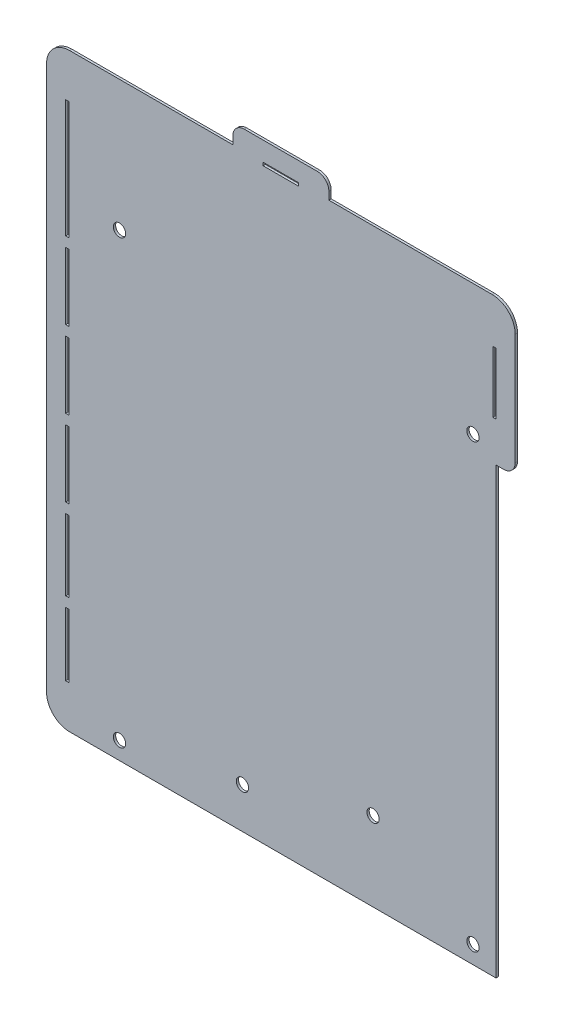
SolidWorks part; units mm, degrees
material "Plain Carbon Steel"
ref_plane "Front Plane" through (0, 0, 0) normal (0, 0, 1) x (1, 0, 0)
ref_plane "Top Plane" through (0, 0, 0) normal (0, 1, 0) x (1, 0, 0)
ref_plane "Right Plane" through (0, 0, 0) normal (1, 0, 0) x (0, 0, -1)
sketch "Model" plane through (0, 0, 0) normal (0, 0, 1) x (1, 0, 0)
  line L0 (104.1673, 32.1811) -> (4.1672, 32.1811)
  line L1 (104.1673, 155.1806) -> (104.1673, 32.1811)
  line L2 (4.1672, 155.1806) -> (104.1673, 155.1806)
  line L3 (4.1672, 32.1811) -> (4.1672, 155.1806)
  line L4 (44.9158, 146.4259) -> (47.4224, 146.4259)
  line L5 (47.4224, 146.4259) -> (47.4224, 148.9326)
  line L6 (47.4224, 148.9326) -> (44.9158, 148.9326)
  line L7 (44.9158, 148.9326) -> (44.9158, 146.4259)
  line L8 (77.4127, 147.4278) -> (79.9193, 147.4278)
  line L9 (79.9193, 147.4278) -> (79.9193, 149.9344)
  line L10 (79.9193, 149.9344) -> (77.4127, 149.9344)
  line L11 (77.4127, 149.9344) -> (77.4127, 147.4278)
  line L12 (6.3266, 141.9721) -> (8.3592, 141.9721)
  line L13 (8.3592, 141.9721) -> (8.3592, 144.0047)
  line L14 (8.3592, 144.0047) -> (6.3266, 144.0047)
  line L15 (6.3266, 144.0047) -> (6.3266, 141.9721)
  line L16 (6.3266, 121.6529) -> (8.3592, 121.6529)
  line L17 (8.3592, 121.6529) -> (8.3592, 123.6855)
  line L18 (8.3592, 123.6855) -> (6.3266, 123.6855)
  line L19 (6.3266, 123.6855) -> (6.3266, 121.6529)
  line L20 (6.3266, 101.3324) -> (8.3592, 101.3324)
  line L21 (8.3592, 101.3324) -> (8.3592, 103.365)
  line L22 (8.3592, 103.365) -> (6.3266, 103.365)
  line L23 (6.3266, 103.365) -> (6.3266, 101.3324)
  line L24 (6.3266, 81.0118) -> (8.3592, 81.0118)
  line L25 (8.3592, 81.0118) -> (8.3592, 83.0444)
  line L26 (8.3592, 83.0444) -> (6.3266, 83.0444)
  line L27 (6.3266, 83.0444) -> (6.3266, 81.0118)
  line L28 (6.3266, 60.6927) -> (8.3592, 60.6927)
  line L29 (8.3592, 60.6927) -> (8.3592, 62.7253)
  line L30 (8.3592, 62.7253) -> (6.3266, 62.7253)
  line L31 (6.3266, 62.7253) -> (6.3266, 60.6927)
  line L32 (85.9221, 148.4144) -> (87.9547, 148.4144)
  line L33 (87.9547, 148.4144) -> (87.9547, 150.447)
  line L34 (87.9547, 150.447) -> (85.9221, 150.447)
  line L35 (85.9221, 150.447) -> (85.9221, 148.4144)
  line L36 (6.3266, 50.5324) -> (8.3592, 50.5324)
  line L37 (8.3592, 50.5324) -> (8.3592, 52.565)
  line L38 (8.3592, 52.565) -> (6.3266, 52.565)
  line L39 (6.3266, 52.565) -> (6.3266, 50.5324)
  line L40 (6.3266, 42.9118) -> (8.3592, 42.9118)
  line L41 (8.3592, 42.9118) -> (8.3592, 44.9444)
  line L42 (8.3592, 44.9444) -> (6.3266, 44.9444)
  line L43 (6.3266, 44.9444) -> (6.3266, 42.9118)
  line L44 (52.8726, 50.0418) -> (54.3815, 50.0418)
  line L45 (54.3815, 50.0418) -> (54.3815, 51.5508)
  line L46 (54.3815, 51.5508) -> (52.8726, 51.5508)
  line L47 (52.8726, 51.5508) -> (52.8726, 50.0418)
  line L48 (58.4219, 130.1637) -> (60.4545, 130.1637)
  line L49 (60.4545, 130.1637) -> (60.4545, 132.1963)
  line L50 (60.4545, 132.1963) -> (58.4219, 132.1963)
  line L51 (58.4219, 132.1963) -> (58.4219, 130.1637)
  line L52 (97.8807, 141.1439) -> (99.9133, 141.1439)
  line L53 (99.9133, 141.1439) -> (99.9133, 143.1765)
  line L54 (99.9133, 143.1765) -> (97.8807, 143.1765)
  line L55 (97.8807, 143.1765) -> (97.8807, 141.1439)
  line L56 (48.438, 37.3046) -> (48.438, 37.0552)
  line L57 (49.9456, 37.0552) -> (49.9456, 37.3046)
  line L58 (52.8877, 37.3046) -> (52.8877, 37.0552)
  line L59 (54.3967, 37.0552) -> (54.3967, 37.3046)
  line L60 (54.3126, 34.0993) -> (54.3126, 33.8995)
  line L61 (56.7201, 33.8995) -> (56.7201, 34.0993)
  line L62 (46.1133, 34.0993) -> (46.1133, 33.8995)
  line L63 (48.5207, 33.8995) -> (48.5207, 34.0993)
  line L64 (82.9607, 49.0165) -> (84.9933, 49.0165)
  line L65 (84.9933, 49.0165) -> (84.9933, 51.0492)
  line L66 (84.9933, 51.0492) -> (82.9607, 51.0492)
  line L67 (82.9607, 51.0492) -> (82.9607, 49.0165)
  line L68 (29.8828, 70.9163) -> (31.9154, 70.9163)
  line L69 (31.9154, 70.9163) -> (31.9154, 72.9489)
  line L70 (31.9154, 72.9489) -> (29.8828, 72.9489)
  line L71 (29.8828, 72.9489) -> (29.8828, 70.9163)
  line L72 (29.8828, 68.1658) -> (31.9154, 68.1658)
  line L73 (31.9154, 68.1658) -> (31.9154, 70.1984)
  line L74 (31.9154, 70.1984) -> (29.8828, 70.1984)
  line L75 (29.8828, 70.1984) -> (29.8828, 68.1658)
  line L76 (29.8828, 108.6649) -> (31.9154, 108.6649)
  line L77 (31.9154, 108.6649) -> (31.9154, 110.6975)
  line L78 (31.9154, 110.6975) -> (29.8828, 110.6975)
  line L79 (29.8828, 110.6975) -> (29.8828, 108.6649)
  line L80 (29.8828, 111.4141) -> (31.9154, 111.4141)
  line L81 (31.9154, 111.4141) -> (31.9154, 113.4467)
  line L82 (31.9154, 113.4467) -> (29.8828, 113.4467)
  line L83 (29.8828, 113.4467) -> (29.8828, 111.4141)
  line L84 (29.8828, 91.1652) -> (31.9154, 91.1652)
  line L85 (31.9154, 91.1652) -> (31.9154, 93.1978)
  line L86 (31.9154, 93.1978) -> (29.8828, 93.1978)
  line L87 (29.8828, 93.1978) -> (29.8828, 91.1652)
  line L88 (29.8828, 88.4147) -> (31.9154, 88.4147)
  line L89 (31.9154, 88.4147) -> (31.9154, 90.4473)
  line L90 (31.9154, 90.4473) -> (29.8828, 90.4473)
  line L91 (29.8828, 90.4473) -> (29.8828, 88.4147)
  line L92 (29.8828, 128.6658) -> (31.9154, 128.6658)
  line L93 (31.9154, 128.6658) -> (31.9154, 130.6984)
  line L94 (31.9154, 130.6984) -> (29.8828, 130.6984)
  line L95 (29.8828, 130.6984) -> (29.8828, 128.6658)
  line L96 (29.8828, 131.4163) -> (31.9154, 131.4163)
  line L97 (31.9154, 131.4163) -> (31.9154, 133.4489)
  line L98 (31.9154, 133.4489) -> (29.8828, 133.4489)
  line L99 (29.8828, 133.4489) -> (29.8828, 131.4163)
  line L100 (48.1611, 135.1453) -> (50.1937, 135.1453)
  line L101 (50.1937, 135.1453) -> (50.1937, 137.1779)
  line L102 (50.1937, 137.1779) -> (48.1611, 137.1779)
  line L103 (48.1611, 137.1779) -> (48.1611, 135.1453)
  line L104 (11.4074, 121.6529) -> (13.44, 121.6529)
  line L105 (13.44, 121.6529) -> (13.44, 123.6855)
  line L106 (13.44, 123.6855) -> (11.4074, 123.6855)
  line L107 (11.4074, 123.6855) -> (11.4074, 121.6529)
  line L108 (104.1673, 32.1811) -> (4.1672, 32.1811)
  line L109 (104.1673, 155.1806) -> (104.1673, 32.1811)
  line L110 (4.1672, 155.1806) -> (104.1673, 155.1806)
  line L111 (4.1672, 32.1811) -> (4.1672, 155.1806)
  spline S0 degree 3 poles (55.1711, 147.6799) (55.1711, 149.685) (52.1643, 149.685) (52.1643, 147.6799) knots 0 0 0 0 1 1 1 1
  spline S1 degree 3 poles (52.1643, 147.6799) (52.1643, 145.6749) (55.1711, 145.6749) (55.1711, 147.6799) knots 0 0 0 0 1 1 1 1
  spline S2 degree 3 poles (75.1706, 148.6804) (75.1706, 150.6854) (72.1637, 150.6854) (72.1637, 148.6804) knots 0 0 0 0 1 1 1 1
  spline S3 degree 3 poles (72.1637, 148.6804) (72.1637, 146.6754) (75.1706, 146.6754) (75.1706, 148.6804) knots 0 0 0 0 1 1 1 1
  spline S4 degree 3 poles (8.3592, 140.448) (8.3592, 141.8026) (6.3266, 141.8026) (6.3266, 140.448) knots 0 0 0 0 1 1 1 1
  spline S5 degree 3 poles (6.3266, 140.448) (6.3266, 139.0934) (8.3592, 139.0934) (8.3592, 140.448) knots 0 0 0 0 1 1 1 1
  spline S6 degree 3 poles (8.3592, 137.9083) (8.3592, 139.2629) (6.3266, 139.2629) (6.3266, 137.9083) knots 0 0 0 0 1 1 1 1
  spline S7 degree 3 poles (6.3266, 137.9083) (6.3266, 136.5537) (8.3592, 136.5537) (8.3592, 137.9083) knots 0 0 0 0 1 1 1 1
  spline S8 degree 3 poles (8.3592, 135.3686) (8.3592, 136.7232) (6.3266, 136.7232) (6.3266, 135.3686) knots 0 0 0 0 1 1 1 1
  spline S9 degree 3 poles (6.3266, 135.3686) (6.3266, 134.0139) (8.3592, 134.0139) (8.3592, 135.3686) knots 0 0 0 0 1 1 1 1
  spline S10 degree 3 poles (8.3592, 132.8288) (8.3592, 134.1834) (6.3266, 134.1834) (6.3266, 132.8288) knots 0 0 0 0 1 1 1 1
  spline S11 degree 3 poles (6.3266, 132.8288) (6.3266, 131.4742) (8.3592, 131.4742) (8.3592, 132.8288) knots 0 0 0 0 1 1 1 1
  spline S12 degree 3 poles (8.3592, 130.2891) (8.3592, 131.6437) (6.3266, 131.6437) (6.3266, 130.2891) knots 0 0 0 0 1 1 1 1
  spline S13 degree 3 poles (6.3266, 130.2891) (6.3266, 128.9331) (8.3592, 128.9331) (8.3592, 130.2891) knots 0 0 0 0 1 1 1 1
  spline S14 degree 3 poles (8.3592, 127.748) (8.3592, 129.1026) (6.3266, 129.1026) (6.3266, 127.748) knots 0 0 0 0 1 1 1 1
  spline S15 degree 3 poles (6.3266, 127.748) (6.3266, 126.3934) (8.3592, 126.3934) (8.3592, 127.748) knots 0 0 0 0 1 1 1 1
  spline S16 degree 3 poles (8.3592, 120.1288) (8.3592, 121.4834) (6.3266, 121.4834) (6.3266, 120.1288) knots 0 0 0 0 1 1 1 1
  spline S17 degree 3 poles (6.3266, 120.1288) (6.3266, 118.7742) (8.3592, 118.7742) (8.3592, 120.1288) knots 0 0 0 0 1 1 1 1
  spline S18 degree 3 poles (8.3592, 117.5891) (8.3592, 118.9437) (6.3266, 118.9437) (6.3266, 117.5891) knots 0 0 0 0 1 1 1 1
  spline S19 degree 3 poles (6.3266, 117.5891) (6.3266, 116.2331) (8.3592, 116.2331) (8.3592, 117.5891) knots 0 0 0 0 1 1 1 1
  spline S20 degree 3 poles (8.3592, 115.048) (8.3592, 116.4026) (6.3266, 116.4026) (6.3266, 115.048) knots 0 0 0 0 1 1 1 1
  spline S21 degree 3 poles (6.3266, 115.048) (6.3266, 113.6934) (8.3592, 113.6934) (8.3592, 115.048) knots 0 0 0 0 1 1 1 1
  spline S22 degree 3 poles (8.3592, 112.5083) (8.3592, 113.8629) (6.3266, 113.8629) (6.3266, 112.5083) knots 0 0 0 0 1 1 1 1
  spline S23 degree 3 poles (6.3266, 112.5083) (6.3266, 111.1537) (8.3592, 111.1537) (8.3592, 112.5083) knots 0 0 0 0 1 1 1 1
  spline S24 degree 3 poles (8.3592, 109.9686) (8.3592, 111.3232) (6.3266, 111.3232) (6.3266, 109.9686) knots 0 0 0 0 1 1 1 1
  spline S25 degree 3 poles (6.3266, 109.9686) (6.3266, 108.6139) (8.3592, 108.6139) (8.3592, 109.9686) knots 0 0 0 0 1 1 1 1
  spline S26 degree 3 poles (8.3592, 107.4288) (8.3592, 108.7834) (6.3266, 108.7834) (6.3266, 107.4288) knots 0 0 0 0 1 1 1 1
  spline S27 degree 3 poles (6.3266, 107.4288) (6.3266, 106.0742) (8.3592, 106.0742) (8.3592, 107.4288) knots 0 0 0 0 1 1 1 1
  spline S28 degree 3 poles (8.3592, 99.8083) (8.3592, 101.1629) (6.3266, 101.1629) (6.3266, 99.8083) knots 0 0 0 0 1 1 1 1
  spline S29 degree 3 poles (6.3266, 99.8083) (6.3266, 98.4537) (8.3592, 98.4537) (8.3592, 99.8083) knots 0 0 0 0 1 1 1 1
  spline S30 degree 3 poles (8.3592, 97.2686) (8.3592, 98.6232) (6.3266, 98.6232) (6.3266, 97.2686) knots 0 0 0 0 1 1 1 1
  spline S31 degree 3 poles (6.3266, 97.2686) (6.3266, 95.9139) (8.3592, 95.9139) (8.3592, 97.2686) knots 0 0 0 0 1 1 1 1
  spline S32 degree 3 poles (8.3592, 94.7288) (8.3592, 96.0834) (6.3266, 96.0834) (6.3266, 94.7288) knots 0 0 0 0 1 1 1 1
  spline S33 degree 3 poles (6.3266, 94.7288) (6.3266, 93.3742) (8.3592, 93.3742) (8.3592, 94.7288) knots 0 0 0 0 1 1 1 1
  spline S34 degree 3 poles (8.3592, 92.1891) (8.3592, 93.5437) (6.3266, 93.5437) (6.3266, 92.1891) knots 0 0 0 0 1 1 1 1
  spline S35 degree 3 poles (6.3266, 92.1891) (6.3266, 90.8331) (8.3592, 90.8331) (8.3592, 92.1891) knots 0 0 0 0 1 1 1 1
  spline S36 degree 3 poles (8.3592, 89.648) (8.3592, 91.0026) (6.3266, 91.0026) (6.3266, 89.648) knots 0 0 0 0 1 1 1 1
  spline S37 degree 3 poles (6.3266, 89.648) (6.3266, 88.2934) (8.3592, 88.2934) (8.3592, 89.648) knots 0 0 0 0 1 1 1 1
  spline S38 degree 3 poles (8.3592, 87.1083) (8.3592, 88.4629) (6.3266, 88.4629) (6.3266, 87.1083) knots 0 0 0 0 1 1 1 1
  spline S39 degree 3 poles (6.3266, 87.1083) (6.3266, 85.7537) (8.3592, 85.7537) (8.3592, 87.1083) knots 0 0 0 0 1 1 1 1
  spline S40 degree 3 poles (8.3592, 79.4891) (8.3592, 80.8437) (6.3266, 80.8437) (6.3266, 79.4891) knots 0 0 0 0 1 1 1 1
  spline S41 degree 3 poles (6.3266, 79.4891) (6.3266, 78.1331) (8.3592, 78.1331) (8.3592, 79.4891) knots 0 0 0 0 1 1 1 1
  spline S42 degree 3 poles (8.3592, 76.948) (8.3592, 78.3026) (6.3266, 78.3026) (6.3266, 76.948) knots 0 0 0 0 1 1 1 1
  spline S43 degree 3 poles (6.3266, 76.948) (6.3266, 75.5934) (8.3592, 75.5934) (8.3592, 76.948) knots 0 0 0 0 1 1 1 1
  spline S44 degree 3 poles (8.3592, 74.4083) (8.3592, 75.7629) (6.3266, 75.7629) (6.3266, 74.4083) knots 0 0 0 0 1 1 1 1
  spline S45 degree 3 poles (6.3266, 74.4083) (6.3266, 73.0537) (8.3592, 73.0537) (8.3592, 74.4083) knots 0 0 0 0 1 1 1 1
  spline S46 degree 3 poles (8.3592, 71.8685) (8.3592, 73.2232) (6.3266, 73.2232) (6.3266, 71.8685) knots 0 0 0 0 1 1 1 1
  spline S47 degree 3 poles (6.3266, 71.8685) (6.3266, 70.5139) (8.3592, 70.5139) (8.3592, 71.8685) knots 0 0 0 0 1 1 1 1
  spline S48 degree 3 poles (8.3592, 69.3288) (8.3592, 70.6834) (6.3266, 70.6834) (6.3266, 69.3288) knots 0 0 0 0 1 1 1 1
  spline S49 degree 3 poles (6.3266, 69.3288) (6.3266, 67.9742) (8.3592, 67.9742) (8.3592, 69.3288) knots 0 0 0 0 1 1 1 1
  spline S50 degree 3 poles (8.3592, 66.7891) (8.3592, 68.1437) (6.3266, 68.1437) (6.3266, 66.7891) knots 0 0 0 0 1 1 1 1
  spline S51 degree 3 poles (6.3266, 66.7891) (6.3266, 65.4331) (8.3592, 65.4331) (8.3592, 66.7891) knots 0 0 0 0 1 1 1 1
  spline S52 degree 3 poles (8.3592, 59.1686) (8.3592, 60.5232) (6.3266, 60.5232) (6.3266, 59.1686) knots 0 0 0 0 1 1 1 1
  spline S53 degree 3 poles (6.3266, 59.1686) (6.3266, 57.8139) (8.3592, 57.8139) (8.3592, 59.1686) knots 0 0 0 0 1 1 1 1
  spline S54 degree 3 poles (8.3592, 56.6288) (8.3592, 57.9834) (6.3266, 57.9834) (6.3266, 56.6288) knots 0 0 0 0 1 1 1 1
  spline S55 degree 3 poles (6.3266, 56.6288) (6.3266, 55.2742) (8.3592, 55.2742) (8.3592, 56.6288) knots 0 0 0 0 1 1 1 1
  spline S56 degree 3 poles (8.3592, 54.0891) (8.3592, 55.4437) (6.3266, 55.4437) (6.3266, 54.0891) knots 0 0 0 0 1 1 1 1
  spline S57 degree 3 poles (6.3266, 54.0891) (6.3266, 52.7331) (8.3592, 52.7331) (8.3592, 54.0891) knots 0 0 0 0 1 1 1 1
  spline S58 degree 3 poles (85.4149, 149.4301) (85.4149, 150.7847) (83.3823, 150.7847) (83.3823, 149.4301) knots 0 0 0 0 1 1 1 1
  spline S59 degree 3 poles (83.3823, 149.4301) (83.3823, 148.0754) (85.4149, 148.0754) (85.4149, 149.4301) knots 0 0 0 0 1 1 1 1
  spline S60 degree 3 poles (8.3592, 49.0083) (8.3592, 50.3629) (6.3266, 50.3629) (6.3266, 49.0083) knots 0 0 0 0 1 1 1 1
  spline S61 degree 3 poles (6.3266, 49.0083) (6.3266, 47.6537) (8.3592, 47.6537) (8.3592, 49.0083) knots 0 0 0 0 1 1 1 1
  spline S62 degree 3 poles (8.3592, 41.3891) (8.3592, 42.7437) (6.3266, 42.7437) (6.3266, 41.3891) knots 0 0 0 0 1 1 1 1
  spline S63 degree 3 poles (6.3266, 41.3891) (6.3266, 40.0331) (8.3592, 40.0331) (8.3592, 41.3891) knots 0 0 0 0 1 1 1 1
  spline S64 degree 3 poles (54.3815, 52.0661) (54.3815, 53.0721) (52.8726, 53.0721) (52.8726, 52.0661) knots 0 0 0 0 1 1 1 1
  spline S65 degree 3 poles (52.8726, 52.0661) (52.8726, 51.0602) (54.3815, 51.0602) (54.3815, 52.0661) knots 0 0 0 0 1 1 1 1
  spline S66 degree 3 poles (55.6507, 50.797) (55.6507, 51.8029) (54.1417, 51.8029) (54.1417, 50.797) knots 0 0 0 0 1 1 1 1
  spline S67 degree 3 poles (54.1417, 50.797) (54.1417, 49.791) (55.6507, 49.791) (55.6507, 50.797) knots 0 0 0 0 1 1 1 1
  spline S68 degree 3 poles (55.6507, 52.0661) (55.6507, 53.0721) (54.1417, 53.0721) (54.1417, 52.0661) knots 0 0 0 0 1 1 1 1
  spline S69 degree 3 poles (54.1417, 52.0661) (54.1417, 51.0602) (55.6507, 51.0602) (55.6507, 52.0661) knots 0 0 0 0 1 1 1 1
  spline S70 degree 3 poles (56.9212, 50.797) (56.9212, 51.8029) (55.4123, 51.8029) (55.4123, 50.797) knots 0 0 0 0 1 1 1 1
  spline S71 degree 3 poles (55.4123, 50.797) (55.4123, 49.791) (56.9212, 49.791) (56.9212, 50.797) knots 0 0 0 0 1 1 1 1
  spline S72 degree 3 poles (56.9212, 52.0661) (56.9212, 53.0721) (55.4123, 53.0721) (55.4123, 52.0661) knots 0 0 0 0 1 1 1 1
  spline S73 degree 3 poles (55.4123, 52.0661) (55.4123, 51.0602) (56.9212, 51.0602) (56.9212, 52.0661) knots 0 0 0 0 1 1 1 1
  spline S74 degree 3 poles (58.1904, 50.797) (58.1904, 51.8029) (56.6828, 51.8029) (56.6828, 50.797) knots 0 0 0 0 1 1 1 1
  spline S75 degree 3 poles (56.6828, 50.797) (56.6828, 49.791) (58.1904, 49.791) (58.1904, 50.797) knots 0 0 0 0 1 1 1 1
  spline S76 degree 3 poles (58.1904, 52.0661) (58.1904, 53.0721) (56.6828, 53.0721) (56.6828, 52.0661) knots 0 0 0 0 1 1 1 1
  spline S77 degree 3 poles (56.6828, 52.0661) (56.6828, 51.0602) (58.1904, 51.0602) (58.1904, 52.0661) knots 0 0 0 0 1 1 1 1
  spline S78 degree 3 poles (59.461, 50.797) (59.461, 51.8029) (57.952, 51.8029) (57.952, 50.797) knots 0 0 0 0 1 1 1 1
  spline S79 degree 3 poles (57.952, 50.797) (57.952, 49.791) (59.461, 49.791) (59.461, 50.797) knots 0 0 0 0 1 1 1 1
  spline S80 degree 3 poles (59.461, 52.0661) (59.461, 53.0721) (57.952, 53.0721) (57.952, 52.0661) knots 0 0 0 0 1 1 1 1
  spline S81 degree 3 poles (57.952, 52.0661) (57.952, 51.0602) (59.461, 51.0602) (59.461, 52.0661) knots 0 0 0 0 1 1 1 1
  spline S82 degree 3 poles (57.9148, 131.1793) (57.9148, 132.5353) (55.8822, 132.5353) (55.8822, 131.1793) knots 0 0 0 0 1 1 1 1
  spline S83 degree 3 poles (55.8822, 131.1793) (55.8822, 129.8247) (57.9148, 129.8247) (57.9148, 131.1793) knots 0 0 0 0 1 1 1 1
  spline S84 degree 3 poles (63.2437, 36.9311) (63.2437, 37.9371) (61.7347, 37.9371) (61.7347, 36.9311) knots 0 0 0 0 1 1 1 1
  spline S85 degree 3 poles (61.7347, 36.9311) (61.7347, 35.9252) (63.2437, 35.9252) (63.2437, 36.9311) knots 0 0 0 0 1 1 1 1
  spline S86 degree 3 poles (71.2239, 36.9311) (71.2239, 37.9371) (69.715, 37.9371) (69.715, 36.9311) knots 0 0 0 0 1 1 1 1
  spline S87 degree 3 poles (69.715, 36.9311) (69.715, 35.9252) (71.2239, 35.9252) (71.2239, 36.9311) knots 0 0 0 0 1 1 1 1
  spline S88 degree 3 poles (102.453, 142.1609) (102.453, 143.5155) (100.4204, 143.5155) (100.4204, 142.1609) knots 0 0 0 0 1 1 1 1
  spline S89 degree 3 poles (100.4204, 142.1609) (100.4204, 140.8063) (102.453, 140.8063) (102.453, 142.1609) knots 0 0 0 0 1 1 1 1
  spline S90 degree 3 poles (99.9133, 129.4609) (99.9133, 130.8155) (97.8807, 130.8155) (97.8807, 129.4609) knots 0 0 0 0 1 1 1 1
  spline S91 degree 3 poles (97.8807, 129.4609) (97.8807, 128.1063) (99.9133, 128.1063) (99.9133, 129.4609) knots 0 0 0 0 1 1 1 1
  spline S92 degree 3 poles (102.453, 139.6198) (102.453, 140.9744) (100.4204, 140.9744) (100.4204, 139.6198) knots 0 0 0 0 1 1 1 1
  spline S93 degree 3 poles (100.4204, 139.6198) (100.4204, 138.2652) (102.453, 138.2652) (102.453, 139.6198) knots 0 0 0 0 1 1 1 1
  spline S94 degree 3 poles (99.9133, 126.9198) (99.9133, 128.2744) (97.8807, 128.2744) (97.8807, 126.9198) knots 0 0 0 0 1 1 1 1
  spline S95 degree 3 poles (97.8807, 126.9198) (97.8807, 125.5652) (99.9133, 125.5652) (99.9133, 126.9198) knots 0 0 0 0 1 1 1 1
  spline S96 degree 3 poles (102.453, 137.0801) (102.453, 138.4347) (100.4204, 138.4347) (100.4204, 137.0801) knots 0 0 0 0 1 1 1 1
  spline S97 degree 3 poles (100.4204, 137.0801) (100.4204, 135.7255) (102.453, 135.7255) (102.453, 137.0801) knots 0 0 0 0 1 1 1 1
  spline S98 degree 3 poles (99.9133, 124.3801) (99.9133, 125.7347) (97.8807, 125.7347) (97.8807, 124.3801) knots 0 0 0 0 1 1 1 1
  spline S99 degree 3 poles (97.8807, 124.3801) (97.8807, 123.0255) (99.9133, 123.0255) (99.9133, 124.3801) knots 0 0 0 0 1 1 1 1
  spline S100 degree 3 poles (102.453, 134.5403) (102.453, 135.895) (100.4204, 135.895) (100.4204, 134.5403) knots 0 0 0 0 1 1 1 1
  spline S101 degree 3 poles (100.4204, 134.5403) (100.4204, 133.1857) (102.453, 133.1857) (102.453, 134.5403) knots 0 0 0 0 1 1 1 1
  spline S102 degree 3 poles (99.9133, 121.8404) (99.9133, 123.195) (97.8807, 123.195) (97.8807, 121.8404) knots 0 0 0 0 1 1 1 1
  spline S103 degree 3 poles (97.8807, 121.8404) (97.8807, 120.4857) (99.9133, 120.4857) (99.9133, 121.8404) knots 0 0 0 0 1 1 1 1
  spline S104 degree 3 poles (102.453, 132.0006) (102.453, 133.3552) (100.4204, 133.3552) (100.4204, 132.0006) knots 0 0 0 0 1 1 1 1
  spline S105 degree 3 poles (100.4204, 132.0006) (100.4204, 130.646) (102.453, 130.646) (102.453, 132.0006) knots 0 0 0 0 1 1 1 1
  spline S106 degree 3 poles (99.9133, 119.3006) (99.9133, 120.6552) (97.8807, 120.6552) (97.8807, 119.3006) knots 0 0 0 0 1 1 1 1
  spline S107 degree 3 poles (97.8807, 119.3006) (97.8807, 117.946) (99.9133, 117.946) (99.9133, 119.3006) knots 0 0 0 0 1 1 1 1
  spline S108 degree 3 poles (102.453, 129.4609) (102.453, 130.8155) (100.4204, 130.8155) (100.4204, 129.4609) knots 0 0 0 0 1 1 1 1
  spline S109 degree 3 poles (100.4204, 129.4609) (100.4204, 128.1063) (102.453, 128.1063) (102.453, 129.4609) knots 0 0 0 0 1 1 1 1
  spline S110 degree 3 poles (99.9133, 116.7609) (99.9133, 118.1155) (97.8807, 118.1155) (97.8807, 116.7609) knots 0 0 0 0 1 1 1 1
  spline S111 degree 3 poles (97.8807, 116.7609) (97.8807, 115.4063) (99.9133, 115.4063) (99.9133, 116.7609) knots 0 0 0 0 1 1 1 1
  spline S112 degree 3 poles (102.453, 126.9198) (102.453, 128.2744) (100.4204, 128.2744) (100.4204, 126.9198) knots 0 0 0 0 1 1 1 1
  spline S113 degree 3 poles (100.4204, 126.9198) (100.4204, 125.5652) (102.453, 125.5652) (102.453, 126.9198) knots 0 0 0 0 1 1 1 1
  spline S114 degree 3 poles (99.9133, 114.2198) (99.9133, 115.5744) (97.8807, 115.5744) (97.8807, 114.2198) knots 0 0 0 0 1 1 1 1
  spline S115 degree 3 poles (97.8807, 114.2198) (97.8807, 112.8652) (99.9133, 112.8652) (99.9133, 114.2198) knots 0 0 0 0 1 1 1 1
  spline S116 degree 3 poles (102.453, 124.3801) (102.453, 125.7347) (100.4204, 125.7347) (100.4204, 124.3801) knots 0 0 0 0 1 1 1 1
  spline S117 degree 3 poles (100.4204, 124.3801) (100.4204, 123.0255) (102.453, 123.0255) (102.453, 124.3801) knots 0 0 0 0 1 1 1 1
  spline S118 degree 3 poles (99.9133, 111.6801) (99.9133, 113.0347) (97.8807, 113.0347) (97.8807, 111.6801) knots 0 0 0 0 1 1 1 1
  spline S119 degree 3 poles (97.8807, 111.6801) (97.8807, 110.3255) (99.9133, 110.3255) (99.9133, 111.6801) knots 0 0 0 0 1 1 1 1
  spline S120 degree 3 poles (102.453, 121.8404) (102.453, 123.195) (100.4204, 123.195) (100.4204, 121.8404) knots 0 0 0 0 1 1 1 1
  spline S121 degree 3 poles (100.4204, 121.8404) (100.4204, 120.4857) (102.453, 120.4857) (102.453, 121.8404) knots 0 0 0 0 1 1 1 1
  spline S122 degree 3 poles (99.9133, 109.1404) (99.9133, 110.495) (97.8807, 110.495) (97.8807, 109.1404) knots 0 0 0 0 1 1 1 1
  spline S123 degree 3 poles (97.8807, 109.1404) (97.8807, 107.7857) (99.9133, 107.7857) (99.9133, 109.1404) knots 0 0 0 0 1 1 1 1
  spline S124 degree 3 poles (102.453, 119.3006) (102.453, 120.6552) (100.4204, 120.6552) (100.4204, 119.3006) knots 0 0 0 0 1 1 1 1
  spline S125 degree 3 poles (100.4204, 119.3006) (100.4204, 117.946) (102.453, 117.946) (102.453, 119.3006) knots 0 0 0 0 1 1 1 1
  spline S126 degree 3 poles (99.9133, 106.6006) (99.9133, 107.9552) (97.8807, 107.9552) (97.8807, 106.6006) knots 0 0 0 0 1 1 1 1
  spline S127 degree 3 poles (97.8807, 106.6006) (97.8807, 105.246) (99.9133, 105.246) (99.9133, 106.6006) knots 0 0 0 0 1 1 1 1
  spline S128 degree 3 poles (102.453, 116.7609) (102.453, 118.1155) (100.4204, 118.1155) (100.4204, 116.7609) knots 0 0 0 0 1 1 1 1
  spline S129 degree 3 poles (100.4204, 116.7609) (100.4204, 115.4063) (102.453, 115.4063) (102.453, 116.7609) knots 0 0 0 0 1 1 1 1
  spline S130 degree 3 poles (99.9133, 104.0609) (99.9133, 105.4155) (97.8807, 105.4155) (97.8807, 104.0609) knots 0 0 0 0 1 1 1 1
  spline S131 degree 3 poles (97.8807, 104.0609) (97.8807, 102.7063) (99.9133, 102.7063) (99.9133, 104.0609) knots 0 0 0 0 1 1 1 1
  spline S132 degree 3 poles (102.453, 114.2198) (102.453, 115.5744) (100.4204, 115.5744) (100.4204, 114.2198) knots 0 0 0 0 1 1 1 1
  spline S133 degree 3 poles (100.4204, 114.2198) (100.4204, 112.8652) (102.453, 112.8652) (102.453, 114.2198) knots 0 0 0 0 1 1 1 1
  spline S134 degree 3 poles (102.453, 111.6801) (102.453, 113.0347) (100.4204, 113.0347) (100.4204, 111.6801) knots 0 0 0 0 1 1 1 1
  spline S135 degree 3 poles (100.4204, 111.6801) (100.4204, 110.3255) (102.453, 110.3255) (102.453, 111.6801) knots 0 0 0 0 1 1 1 1
  spline S136 degree 3 poles (99.9133, 101.5198) (99.9133, 102.8744) (97.8807, 102.8744) (97.8807, 101.5198) knots 0 0 0 0 1 1 1 1
  spline S137 degree 3 poles (97.8807, 101.5198) (97.8807, 100.1652) (99.9133, 100.1652) (99.9133, 101.5198) knots 0 0 0 0 1 1 1 1
  spline S138 degree 3 poles (102.453, 109.1404) (102.453, 110.495) (100.4204, 110.495) (100.4204, 109.1404) knots 0 0 0 0 1 1 1 1
  spline S139 degree 3 poles (100.4204, 109.1404) (100.4204, 107.7857) (102.453, 107.7857) (102.453, 109.1404) knots 0 0 0 0 1 1 1 1
  spline S140 degree 3 poles (102.453, 104.0609) (102.453, 105.4155) (100.4204, 105.4155) (100.4204, 104.0609) knots 0 0 0 0 1 1 1 1
  spline S141 degree 3 poles (100.4204, 104.0609) (100.4204, 102.7063) (102.453, 102.7063) (102.453, 104.0609) knots 0 0 0 0 1 1 1 1
  spline S142 degree 3 poles (102.453, 101.5198) (102.453, 102.8744) (100.4204, 102.8744) (100.4204, 101.5198) knots 0 0 0 0 1 1 1 1
  spline S143 degree 3 poles (100.4204, 101.5198) (100.4204, 100.1652) (102.453, 100.1652) (102.453, 101.5198) knots 0 0 0 0 1 1 1 1
  spline S144 degree 3 poles (102.453, 98.9801) (102.453, 100.3347) (100.4204, 100.3347) (100.4204, 98.9801) knots 0 0 0 0 1 1 1 1
  spline S145 degree 3 poles (100.4204, 98.9801) (100.4204, 97.6255) (102.453, 97.6255) (102.453, 98.9801) knots 0 0 0 0 1 1 1 1
  spline S146 degree 3 poles (102.453, 96.4404) (102.453, 97.795) (100.4204, 97.795) (100.4204, 96.4404) knots 0 0 0 0 1 1 1 1
  spline S147 degree 3 poles (100.4204, 96.4404) (100.4204, 95.0857) (102.453, 95.0857) (102.453, 96.4404) knots 0 0 0 0 1 1 1 1
  spline S148 degree 3 poles (99.9133, 98.9801) (99.9133, 100.3347) (97.8807, 100.3347) (97.8807, 98.9801) knots 0 0 0 0 1 1 1 1
  spline S149 degree 3 poles (97.8807, 98.9801) (97.8807, 97.6255) (99.9133, 97.6255) (99.9133, 98.9801) knots 0 0 0 0 1 1 1 1
  spline S150 degree 3 poles (99.9133, 96.4404) (99.9133, 97.795) (97.8807, 97.795) (97.8807, 96.4404) knots 0 0 0 0 1 1 1 1
  spline S151 degree 3 poles (97.8807, 96.4404) (97.8807, 95.0857) (99.9133, 95.0857) (99.9133, 96.4404) knots 0 0 0 0 1 1 1 1
  spline S152 degree 3 poles (99.9133, 139.6198) (99.9133, 140.9744) (97.8807, 140.9744) (97.8807, 139.6198) knots 0 0 0 0 1 1 1 1
  spline S153 degree 3 poles (97.8807, 139.6198) (97.8807, 138.2652) (99.9133, 138.2652) (99.9133, 139.6198) knots 0 0 0 0 1 1 1 1
  spline S154 degree 3 poles (99.9133, 137.0801) (99.9133, 138.4347) (97.8807, 138.4347) (97.8807, 137.0801) knots 0 0 0 0 1 1 1 1
  spline S155 degree 3 poles (97.8807, 137.0801) (97.8807, 135.7255) (99.9133, 135.7255) (99.9133, 137.0801) knots 0 0 0 0 1 1 1 1
  spline S156 degree 3 poles (99.9133, 134.5403) (99.9133, 135.895) (97.8807, 135.895) (97.8807, 134.5403) knots 0 0 0 0 1 1 1 1
  spline S157 degree 3 poles (97.8807, 134.5403) (97.8807, 133.1857) (99.9133, 133.1857) (99.9133, 134.5403) knots 0 0 0 0 1 1 1 1
  spline S158 degree 3 poles (99.9133, 132.0006) (99.9133, 133.3552) (97.8807, 133.3552) (97.8807, 132.0006) knots 0 0 0 0 1 1 1 1
  spline S159 degree 3 poles (97.8807, 132.0006) (97.8807, 130.646) (99.9133, 130.646) (99.9133, 132.0006) knots 0 0 0 0 1 1 1 1
  spline S160 degree 3 poles (99.9133, 93.9006) (99.9133, 95.2552) (97.8807, 95.2552) (97.8807, 93.9006) knots 0 0 0 0 1 1 1 1
  spline S161 degree 3 poles (97.8807, 93.9006) (97.8807, 92.546) (99.9133, 92.546) (99.9133, 93.9006) knots 0 0 0 0 1 1 1 1
  spline S162 degree 3 poles (102.453, 93.9006) (102.453, 95.2552) (100.4204, 95.2552) (100.4204, 93.9006) knots 0 0 0 0 1 1 1 1
  spline S163 degree 3 poles (100.4204, 93.9006) (100.4204, 92.546) (102.453, 92.546) (102.453, 93.9006) knots 0 0 0 0 1 1 1 1
  spline S164 degree 3 poles (102.453, 106.6006) (102.453, 107.9552) (100.4204, 107.9552) (100.4204, 106.6006) knots 0 0 0 0 1 1 1 1
  spline S165 degree 3 poles (100.4204, 106.6006) (100.4204, 105.246) (102.453, 105.246) (102.453, 106.6006) knots 0 0 0 0 1 1 1 1
  spline S166 degree 3 poles (99.9133, 91.3609) (99.9133, 92.7155) (97.8807, 92.7155) (97.8807, 91.3609) knots 0 0 0 0 1 1 1 1
  spline S167 degree 3 poles (97.8807, 91.3609) (97.8807, 90.0063) (99.9133, 90.0063) (99.9133, 91.3609) knots 0 0 0 0 1 1 1 1
  spline S168 degree 3 poles (102.453, 91.3609) (102.453, 92.7155) (100.4204, 92.7155) (100.4204, 91.3609) knots 0 0 0 0 1 1 1 1
  spline S169 degree 3 poles (100.4204, 91.3609) (100.4204, 90.0063) (102.453, 90.0063) (102.453, 91.3609) knots 0 0 0 0 1 1 1 1
  spline S170 degree 3 poles (99.9133, 88.8198) (99.9133, 90.1744) (97.8807, 90.1744) (97.8807, 88.8198) knots 0 0 0 0 1 1 1 1
  spline S171 degree 3 poles (97.8807, 88.8198) (97.8807, 87.4652) (99.9133, 87.4652) (99.9133, 88.8198) knots 0 0 0 0 1 1 1 1
  spline S172 degree 3 poles (102.453, 88.8198) (102.453, 90.1744) (100.4204, 90.1744) (100.4204, 88.8198) knots 0 0 0 0 1 1 1 1
  spline S173 degree 3 poles (100.4204, 88.8198) (100.4204, 87.4652) (102.453, 87.4652) (102.453, 88.8198) knots 0 0 0 0 1 1 1 1
  spline S174 degree 3 poles (99.9133, 86.2801) (99.9133, 87.6347) (97.8807, 87.6347) (97.8807, 86.2801) knots 0 0 0 0 1 1 1 1
  spline S175 degree 3 poles (97.8807, 86.2801) (97.8807, 84.9255) (99.9133, 84.9255) (99.9133, 86.2801) knots 0 0 0 0 1 1 1 1
  spline S176 degree 3 poles (102.453, 86.2801) (102.453, 87.6347) (100.4204, 87.6347) (100.4204, 86.2801) knots 0 0 0 0 1 1 1 1
  spline S177 degree 3 poles (100.4204, 86.2801) (100.4204, 84.9255) (102.453, 84.9255) (102.453, 86.2801) knots 0 0 0 0 1 1 1 1
  spline S178 degree 3 poles (99.9133, 83.7404) (99.9133, 85.095) (97.8807, 85.095) (97.8807, 83.7404) knots 0 0 0 0 1 1 1 1
  spline S179 degree 3 poles (97.8807, 83.7404) (97.8807, 82.3857) (99.9133, 82.3857) (99.9133, 83.7404) knots 0 0 0 0 1 1 1 1
  spline S180 degree 3 poles (102.453, 83.7404) (102.453, 85.095) (100.4204, 85.095) (100.4204, 83.7404) knots 0 0 0 0 1 1 1 1
  spline S181 degree 3 poles (100.4204, 83.7404) (100.4204, 82.3857) (102.453, 82.3857) (102.453, 83.7404) knots 0 0 0 0 1 1 1 1
  spline S182 degree 3 poles (99.9133, 81.2006) (99.9133, 82.5552) (97.8807, 82.5552) (97.8807, 81.2006) knots 0 0 0 0 1 1 1 1
  spline S183 degree 3 poles (97.8807, 81.2006) (97.8807, 79.846) (99.9133, 79.846) (99.9133, 81.2006) knots 0 0 0 0 1 1 1 1
  spline S184 degree 3 poles (102.453, 81.2006) (102.453, 82.5552) (100.4204, 82.5552) (100.4204, 81.2006) knots 0 0 0 0 1 1 1 1
  spline S185 degree 3 poles (100.4204, 81.2006) (100.4204, 79.846) (102.453, 79.846) (102.453, 81.2006) knots 0 0 0 0 1 1 1 1
  spline S186 degree 3 poles (49.9456, 37.3046) (49.9456, 38.3106) (48.438, 38.3106) (48.438, 37.3046) knots 0 0 0 0 1 1 1 1
  spline S187 degree 3 poles (48.438, 37.0552) (48.438, 36.0492) (49.9456, 36.0492) (49.9456, 37.0552) knots 0 0 0 0 1 1 1 1
  spline S188 degree 3 poles (54.3967, 37.3046) (54.3967, 38.3106) (52.8877, 38.3106) (52.8877, 37.3046) knots 0 0 0 0 1 1 1 1
  spline S189 degree 3 poles (52.8877, 37.0552) (52.8877, 36.0492) (54.3967, 36.0492) (54.3967, 37.0552) knots 0 0 0 0 1 1 1 1
  spline S190 degree 3 poles (56.7201, 34.0993) (56.7201, 35.7047) (54.3126, 35.7047) (54.3126, 34.0993) knots 0 0 0 0 1 1 1 1
  spline S191 degree 3 poles (54.3126, 33.8995) (54.3126, 32.2941) (56.7201, 32.2941) (56.7201, 33.8995) knots 0 0 0 0 1 1 1 1
  spline S192 degree 3 poles (48.5207, 34.0993) (48.5207, 35.7047) (46.1133, 35.7047) (46.1133, 34.0993) knots 0 0 0 0 1 1 1 1
  spline S193 degree 3 poles (46.1133, 33.8995) (46.1133, 32.2941) (48.5207, 32.2941) (48.5207, 33.8995) knots 0 0 0 0 1 1 1 1
  spline S194 degree 3 poles (54.4711, 34.0001) (54.4711, 34.9054) (53.1123, 34.9054) (53.1123, 34.0001) knots 0 0 0 0 1 1 1 1
  spline S195 degree 3 poles (53.1123, 34.0001) (53.1123, 33.0933) (54.4711, 33.0933) (54.4711, 34.0001) knots 0 0 0 0 1 1 1 1
  spline S196 degree 3 poles (49.721, 34.0001) (49.721, 34.9054) (48.3623, 34.9054) (48.3623, 34.0001) knots 0 0 0 0 1 1 1 1
  spline S197 degree 3 poles (48.3623, 34.0001) (48.3623, 33.0933) (49.721, 33.0933) (49.721, 34.0001) knots 0 0 0 0 1 1 1 1
  spline S198 degree 3 poles (84.606, 43.6822) (84.606, 46.2205) (80.7985, 46.2205) (80.7985, 43.6822) knots 0 0 0 0 1 1 1 1
  spline S199 degree 3 poles (80.7985, 43.6822) (80.7985, 41.1438) (84.606, 41.1438) (84.606, 43.6822) knots 0 0 0 0 1 1 1 1
  spline S200 degree 3 poles (96.0355, 43.6822) (96.0355, 46.2205) (92.228, 46.2205) (92.228, 43.6822) knots 0 0 0 0 1 1 1 1
  spline S201 degree 3 poles (92.228, 43.6822) (92.228, 41.1438) (96.0355, 41.1438) (96.0355, 43.6822) knots 0 0 0 0 1 1 1 1
  spline S202 degree 3 poles (93.8775, 52.5719) (93.8775, 53.9265) (91.8462, 53.9265) (91.8462, 52.5719) knots 0 0 0 0 1 1 1 1
  spline S203 degree 3 poles (91.8462, 52.5719) (91.8462, 51.2173) (93.8775, 51.2173) (93.8775, 52.5719) knots 0 0 0 0 1 1 1 1
  spline S204 degree 3 poles (92.6124, 50.0322) (92.6124, 51.3868) (90.5812, 51.3868) (90.5812, 50.0322) knots 0 0 0 0 1 1 1 1
  spline S205 degree 3 poles (90.5812, 50.0322) (90.5812, 48.6775) (92.6124, 48.6775) (92.6124, 50.0322) knots 0 0 0 0 1 1 1 1
  spline S206 degree 3 poles (91.3377, 52.5719) (91.3377, 53.9265) (89.3065, 53.9265) (89.3065, 52.5719) knots 0 0 0 0 1 1 1 1
  spline S207 degree 3 poles (89.3065, 52.5719) (89.3065, 51.2173) (91.3377, 51.2173) (91.3377, 52.5719) knots 0 0 0 0 1 1 1 1
  spline S208 degree 3 poles (90.0727, 50.0322) (90.0727, 51.3868) (88.0415, 51.3868) (88.0415, 50.0322) knots 0 0 0 0 1 1 1 1
  spline S209 degree 3 poles (88.0415, 50.0322) (88.0415, 48.6775) (90.0727, 48.6775) (90.0727, 50.0322) knots 0 0 0 0 1 1 1 1
  spline S210 degree 3 poles (88.798, 52.5719) (88.798, 53.9265) (86.7654, 53.9265) (86.7654, 52.5719) knots 0 0 0 0 1 1 1 1
  spline S211 degree 3 poles (86.7654, 52.5719) (86.7654, 51.2173) (88.798, 51.2173) (88.798, 52.5719) knots 0 0 0 0 1 1 1 1
  spline S212 degree 3 poles (87.533, 50.0322) (87.533, 51.3868) (85.5018, 51.3868) (85.5018, 50.0322) knots 0 0 0 0 1 1 1 1
  spline S213 degree 3 poles (85.5018, 50.0322) (85.5018, 48.6775) (87.533, 48.6775) (87.533, 50.0322) knots 0 0 0 0 1 1 1 1
  spline S214 degree 3 poles (86.2583, 52.5719) (86.2583, 53.9265) (84.2257, 53.9265) (84.2257, 52.5719) knots 0 0 0 0 1 1 1 1
  spline S215 degree 3 poles (84.2257, 52.5719) (84.2257, 51.2173) (86.2583, 51.2173) (86.2583, 52.5719) knots 0 0 0 0 1 1 1 1
  spline S216 degree 3 poles (82.1945, 46.7331) (82.1945, 48.7644) (79.1462, 48.7644) (79.1462, 46.7331) knots 0 0 0 0 1 1 1 1
  spline S217 degree 3 poles (79.1462, 46.7331) (79.1462, 44.7005) (82.1945, 44.7005) (82.1945, 46.7331) knots 0 0 0 0 1 1 1 1
  spline S218 degree 3 poles (97.6877, 46.7304) (97.6877, 48.7616) (94.6395, 48.7616) (94.6395, 46.7304) knots 0 0 0 0 1 1 1 1
  spline S219 degree 3 poles (94.6395, 46.7304) (94.6395, 44.6978) (97.6877, 44.6978) (97.6877, 46.7304) knots 0 0 0 0 1 1 1 1
  spline S220 degree 3 poles (93.5178, 38.7819) (93.5178, 40.1365) (91.4852, 40.1365) (91.4852, 38.7819) knots 0 0 0 0 1 1 1 1
  spline S221 degree 3 poles (91.4852, 38.7819) (91.4852, 37.4272) (93.5178, 37.4272) (93.5178, 38.7819) knots 0 0 0 0 1 1 1 1
  spline S222 degree 3 poles (85.3488, 38.7819) (85.3488, 40.1365) (83.3162, 40.1365) (83.3162, 38.7819) knots 0 0 0 0 1 1 1 1
  spline S223 degree 3 poles (83.3162, 38.7819) (83.3162, 37.4272) (85.3488, 37.4272) (85.3488, 38.7819) knots 0 0 0 0 1 1 1 1
  spline S224 degree 3 poles (96.0575, 38.7819) (96.0575, 40.1365) (94.0249, 40.1365) (94.0249, 38.7819) knots 0 0 0 0 1 1 1 1
  spline S225 degree 3 poles (94.0249, 38.7819) (94.0249, 37.4272) (96.0575, 37.4272) (96.0575, 38.7819) knots 0 0 0 0 1 1 1 1
  spline S226 degree 3 poles (82.8091, 38.7819) (82.8091, 40.1365) (80.7765, 40.1365) (80.7765, 38.7819) knots 0 0 0 0 1 1 1 1
  spline S227 degree 3 poles (80.7765, 38.7819) (80.7765, 37.4272) (82.8091, 37.4272) (82.8091, 38.7819) knots 0 0 0 0 1 1 1 1
  spline S228 degree 3 poles (102.9215, 36.1815) (102.9215, 37.7029) (101.6882, 38.9362) (100.1668, 38.9362) knots 0 0 0 0 1 1 1 1
  spline S229 degree 3 poles (100.1668, 38.9362) (98.6455, 38.9362) (97.4121, 37.7028) (97.4121, 36.1815) knots 0 0 0 0 1 1 1 1
  spline S230 degree 3 poles (97.4121, 36.1815) (97.4121, 34.6601) (98.6455, 33.4268) (100.1668, 33.4268) knots 0 0 0 0 1 1 1 1
  spline S231 degree 3 poles (100.1668, 33.4268) (101.6882, 33.4268) (102.9215, 34.6601) (102.9215, 36.1815) knots 0 0 0 0 1 1 1 1
  spline S232 degree 3 poles (10.9223, 36.1815) (10.9223, 37.7028) (9.689, 38.9362) (8.1676, 38.9362) knots 0 0 0 0 1 1 1 1
  spline S233 degree 3 poles (8.1676, 38.9362) (6.6463, 38.9362) (5.4129, 37.7028) (5.4129, 36.1815) knots 0 0 0 0 1 1 1 1
  spline S234 degree 3 poles (5.4129, 36.1815) (5.4129, 34.6601) (6.6463, 33.4268) (8.1676, 33.4268) knots 0 0 0 0 1 1 1 1
  spline S235 degree 3 poles (8.1676, 33.4268) (9.689, 33.4268) (10.9223, 34.6601) (10.9223, 36.1815) knots 0 0 0 0 1 1 1 1
  spline S236 degree 3 poles (10.9223, 151.1802) (10.9223, 152.7015) (9.689, 153.9349) (8.1676, 153.9349) knots 0 0 0 0 1 1 1 1
  spline S237 degree 3 poles (8.1676, 153.9349) (6.6463, 153.9349) (5.4129, 152.7015) (5.4129, 151.1802) knots 0 0 0 0 1 1 1 1
  spline S238 degree 3 poles (5.4129, 151.1802) (5.4129, 149.6588) (6.6463, 148.4255) (8.1676, 148.4255) knots 0 0 0 0 1 1 1 1
  spline S239 degree 3 poles (8.1676, 148.4255) (9.689, 148.4255) (10.9223, 149.6588) (10.9223, 151.1802) knots 0 0 0 0 1 1 1 1
  spline S240 degree 3 poles (102.9215, 151.1802) (102.9215, 152.7015) (101.6882, 153.9349) (100.1668, 153.9349) knots 0 0 0 0 1 1 1 1
  spline S241 degree 3 poles (100.1668, 153.9349) (98.6455, 153.9349) (97.4121, 152.7015) (97.4121, 151.1802) knots 0 0 0 0 1 1 1 1
  spline S242 degree 3 poles (97.4121, 151.1802) (97.4121, 149.6588) (98.6455, 148.4255) (100.1668, 148.4255) knots 0 0 0 0 1 1 1 1
  spline S243 degree 3 poles (100.1668, 148.4255) (101.6882, 148.4255) (102.9215, 149.6588) (102.9215, 151.1802) knots 0 0 0 0 1 1 1 1
  spline S244 degree 3 poles (44.3218, 98.681) (44.3218, 99.5533) (43.0127, 99.5533) (43.0127, 98.681) knots 0 0 0 0 1 1 1 1
  spline S245 degree 3 poles (43.0127, 98.681) (43.0127, 97.8087) (44.3218, 97.8087) (44.3218, 98.681) knots 0 0 0 0 1 1 1 1
  spline S246 degree 3 poles (43.8216, 138.9322) (43.8216, 139.8045) (42.5125, 139.8045) (42.5125, 138.9322) knots 0 0 0 0 1 1 1 1
  spline S247 degree 3 poles (42.5125, 138.9322) (42.5125, 138.0599) (43.8216, 138.0599) (43.8216, 138.9322) knots 0 0 0 0 1 1 1 1
  spline S248 degree 3 poles (44.3218, 119.1807) (44.3218, 120.053) (43.0127, 120.053) (43.0127, 119.1807) knots 0 0 0 0 1 1 1 1
  spline S249 degree 3 poles (43.0127, 119.1807) (43.0127, 118.3084) (44.3218, 118.3084) (44.3218, 119.1807) knots 0 0 0 0 1 1 1 1
  spline S250 degree 3 poles (41.8221, 76.9301) (41.8221, 77.8024) (40.5143, 77.8024) (40.5143, 76.9301) knots 0 0 0 0 1 1 1 1
  spline S251 degree 3 poles (40.5143, 76.9301) (40.5143, 76.0592) (41.8221, 76.0592) (41.8221, 76.9301) knots 0 0 0 0 1 1 1 1
  spline S252 degree 3 poles (34.4551, 71.9319) (34.4551, 73.2866) (32.4225, 73.2866) (32.4225, 71.9319) knots 0 0 0 0 1 1 1 1
  spline S253 degree 3 poles (32.4225, 71.9319) (32.4225, 70.5773) (34.4551, 70.5773) (34.4551, 71.9319) knots 0 0 0 0 1 1 1 1
  spline S254 degree 3 poles (34.4551, 69.1814) (34.4551, 70.536) (32.4225, 70.536) (32.4225, 69.1814) knots 0 0 0 0 1 1 1 1
  spline S255 degree 3 poles (32.4225, 69.1814) (32.4225, 67.8268) (34.4551, 67.8268) (34.4551, 69.1814) knots 0 0 0 0 1 1 1 1
  spline S256 degree 3 poles (34.4551, 109.6819) (34.4551, 111.0365) (32.4225, 111.0365) (32.4225, 109.6819) knots 0 0 0 0 1 1 1 1
  spline S257 degree 3 poles (32.4225, 109.6819) (32.4225, 108.3273) (34.4551, 108.3273) (34.4551, 109.6819) knots 0 0 0 0 1 1 1 1
  spline S258 degree 3 poles (34.4551, 112.4297) (34.4551, 113.7843) (32.4225, 113.7843) (32.4225, 112.4297) knots 0 0 0 0 1 1 1 1
  spline S259 degree 3 poles (32.4225, 112.4297) (32.4225, 111.0751) (34.4551, 111.0751) (34.4551, 112.4297) knots 0 0 0 0 1 1 1 1
  spline S260 degree 3 poles (34.4551, 92.1808) (34.4551, 93.5354) (32.4225, 93.5354) (32.4225, 92.1808) knots 0 0 0 0 1 1 1 1
  spline S261 degree 3 poles (32.4225, 92.1808) (32.4225, 90.8262) (34.4551, 90.8262) (34.4551, 92.1808) knots 0 0 0 0 1 1 1 1
  spline S262 degree 3 poles (34.4551, 89.4303) (34.4551, 90.7849) (32.4225, 90.7849) (32.4225, 89.4303) knots 0 0 0 0 1 1 1 1
  spline S263 degree 3 poles (32.4225, 89.4303) (32.4225, 88.0757) (34.4551, 88.0757) (34.4551, 89.4303) knots 0 0 0 0 1 1 1 1
  spline S264 degree 3 poles (34.4551, 129.6814) (34.4551, 131.036) (32.4225, 131.036) (32.4225, 129.6814) knots 0 0 0 0 1 1 1 1
  spline S265 degree 3 poles (32.4225, 129.6814) (32.4225, 128.3268) (34.4551, 128.3268) (34.4551, 129.6814) knots 0 0 0 0 1 1 1 1
  spline S266 degree 3 poles (34.4551, 132.432) (34.4551, 133.7866) (32.4225, 133.7866) (32.4225, 132.432) knots 0 0 0 0 1 1 1 1
  spline S267 degree 3 poles (32.4225, 132.432) (32.4225, 131.0773) (34.4551, 131.0773) (34.4551, 132.432) knots 0 0 0 0 1 1 1 1
  spline S268 degree 3 poles (50.1923, 138.7006) (50.1923, 140.0553) (48.1611, 140.0553) (48.1611, 138.7006) knots 0 0 0 0 1 1 1 1
  spline S269 degree 3 poles (48.1611, 138.7006) (48.1611, 137.346) (50.1923, 137.346) (50.1923, 138.7006) knots 0 0 0 0 1 1 1 1
  spline S270 degree 3 poles (52.732, 136.1609) (52.732, 137.5155) (50.7008, 137.5155) (50.7008, 136.1609) knots 0 0 0 0 1 1 1 1
  spline S271 degree 3 poles (50.7008, 136.1609) (50.7008, 134.8063) (52.732, 134.8063) (52.732, 136.1609) knots 0 0 0 0 1 1 1 1
  spline S272 degree 3 poles (52.732, 138.7006) (52.732, 140.0553) (50.7008, 140.0553) (50.7008, 138.7006) knots 0 0 0 0 1 1 1 1
  spline S273 degree 3 poles (50.7008, 138.7006) (50.7008, 137.346) (52.732, 137.346) (52.732, 138.7006) knots 0 0 0 0 1 1 1 1
  spline S274 degree 3 poles (55.2731, 136.1609) (55.2731, 137.5155) (53.2405, 137.5155) (53.2405, 136.1609) knots 0 0 0 0 1 1 1 1
  spline S275 degree 3 poles (53.2405, 136.1609) (53.2405, 134.8063) (55.2731, 134.8063) (55.2731, 136.1609) knots 0 0 0 0 1 1 1 1
  spline S276 degree 3 poles (55.2731, 138.7006) (55.2731, 140.0553) (53.2405, 140.0553) (53.2405, 138.7006) knots 0 0 0 0 1 1 1 1
  spline S277 degree 3 poles (53.2405, 138.7006) (53.2405, 137.346) (55.2731, 137.346) (55.2731, 138.7006) knots 0 0 0 0 1 1 1 1
  spline S278 degree 3 poles (57.8128, 136.1609) (57.8128, 137.5155) (55.7802, 137.5155) (55.7802, 136.1609) knots 0 0 0 0 1 1 1 1
  spline S279 degree 3 poles (55.7802, 136.1609) (55.7802, 134.8063) (57.8128, 134.8063) (57.8128, 136.1609) knots 0 0 0 0 1 1 1 1
  spline S280 degree 3 poles (57.8128, 138.7006) (57.8128, 140.0553) (55.7802, 140.0553) (55.7802, 138.7006) knots 0 0 0 0 1 1 1 1
  spline S281 degree 3 poles (55.7802, 138.7006) (55.7802, 137.346) (57.8128, 137.346) (57.8128, 138.7006) knots 0 0 0 0 1 1 1 1
  spline S282 degree 3 poles (60.3526, 136.1609) (60.3526, 137.5155) (58.32, 137.5155) (58.32, 136.1609) knots 0 0 0 0 1 1 1 1
  spline S283 degree 3 poles (58.32, 136.1609) (58.32, 134.8063) (60.3526, 134.8063) (60.3526, 136.1609) knots 0 0 0 0 1 1 1 1
  spline S284 degree 3 poles (60.3526, 138.7006) (60.3526, 140.0553) (58.32, 140.0553) (58.32, 138.7006) knots 0 0 0 0 1 1 1 1
  spline S285 degree 3 poles (58.32, 138.7006) (58.32, 137.346) (60.3526, 137.346) (60.3526, 138.7006) knots 0 0 0 0 1 1 1 1
  spline S286 degree 3 poles (62.8923, 136.1609) (62.8923, 137.5155) (60.8611, 137.5155) (60.8611, 136.1609) knots 0 0 0 0 1 1 1 1
  spline S287 degree 3 poles (60.8611, 136.1609) (60.8611, 134.8063) (62.8923, 134.8063) (62.8923, 136.1609) knots 0 0 0 0 1 1 1 1
  spline S288 degree 3 poles (62.8923, 138.7006) (62.8923, 140.0553) (60.8611, 140.0553) (60.8611, 138.7006) knots 0 0 0 0 1 1 1 1
  spline S289 degree 3 poles (60.8611, 138.7006) (60.8611, 137.346) (62.8923, 137.346) (62.8923, 138.7006) knots 0 0 0 0 1 1 1 1
  spline S290 degree 3 poles (65.432, 136.1609) (65.432, 137.5155) (63.4008, 137.5155) (63.4008, 136.1609) knots 0 0 0 0 1 1 1 1
  spline S291 degree 3 poles (63.4008, 136.1609) (63.4008, 134.8063) (65.432, 134.8063) (65.432, 136.1609) knots 0 0 0 0 1 1 1 1
  spline S292 degree 3 poles (65.432, 138.7006) (65.432, 140.0553) (63.4008, 140.0553) (63.4008, 138.7006) knots 0 0 0 0 1 1 1 1
  spline S293 degree 3 poles (63.4008, 138.7006) (63.4008, 137.346) (65.432, 137.346) (65.432, 138.7006) knots 0 0 0 0 1 1 1 1
  spline S294 degree 3 poles (67.9731, 136.1609) (67.9731, 137.5155) (65.9405, 137.5155) (65.9405, 136.1609) knots 0 0 0 0 1 1 1 1
  spline S295 degree 3 poles (65.9405, 136.1609) (65.9405, 134.8063) (67.9731, 134.8063) (67.9731, 136.1609) knots 0 0 0 0 1 1 1 1
  spline S296 degree 3 poles (67.9731, 138.7006) (67.9731, 140.0553) (65.9405, 140.0553) (65.9405, 138.7006) knots 0 0 0 0 1 1 1 1
  spline S297 degree 3 poles (65.9405, 138.7006) (65.9405, 137.346) (67.9731, 137.346) (67.9731, 138.7006) knots 0 0 0 0 1 1 1 1
  spline S298 degree 3 poles (70.5128, 136.1609) (70.5128, 137.5155) (68.4802, 137.5155) (68.4802, 136.1609) knots 0 0 0 0 1 1 1 1
  spline S299 degree 3 poles (68.4802, 136.1609) (68.4802, 134.8063) (70.5128, 134.8063) (70.5128, 136.1609) knots 0 0 0 0 1 1 1 1
  spline S300 degree 3 poles (70.5128, 138.7006) (70.5128, 140.0553) (68.4802, 140.0553) (68.4802, 138.7006) knots 0 0 0 0 1 1 1 1
  spline S301 degree 3 poles (68.4802, 138.7006) (68.4802, 137.346) (70.5128, 137.346) (70.5128, 138.7006) knots 0 0 0 0 1 1 1 1
  spline S302 degree 3 poles (73.0526, 136.1609) (73.0526, 137.5155) (71.02, 137.5155) (71.02, 136.1609) knots 0 0 0 0 1 1 1 1
  spline S303 degree 3 poles (71.02, 136.1609) (71.02, 134.8063) (73.0526, 134.8063) (73.0526, 136.1609) knots 0 0 0 0 1 1 1 1
  spline S304 degree 3 poles (73.0526, 138.7006) (73.0526, 140.0553) (71.02, 140.0553) (71.02, 138.7006) knots 0 0 0 0 1 1 1 1
  spline S305 degree 3 poles (71.02, 138.7006) (71.02, 137.346) (73.0526, 137.346) (73.0526, 138.7006) knots 0 0 0 0 1 1 1 1
  spline S306 degree 3 poles (75.5923, 136.1609) (75.5923, 137.5155) (73.5611, 137.5155) (73.5611, 136.1609) knots 0 0 0 0 1 1 1 1
  spline S307 degree 3 poles (73.5611, 136.1609) (73.5611, 134.8063) (75.5923, 134.8063) (75.5923, 136.1609) knots 0 0 0 0 1 1 1 1
  spline S308 degree 3 poles (75.5923, 138.7006) (75.5923, 140.0553) (73.5611, 140.0553) (73.5611, 138.7006) knots 0 0 0 0 1 1 1 1
  spline S309 degree 3 poles (73.5611, 138.7006) (73.5611, 137.346) (75.5923, 137.346) (75.5923, 138.7006) knots 0 0 0 0 1 1 1 1
  spline S310 degree 3 poles (78.132, 136.1609) (78.132, 137.5155) (76.1008, 137.5155) (76.1008, 136.1609) knots 0 0 0 0 1 1 1 1
  spline S311 degree 3 poles (76.1008, 136.1609) (76.1008, 134.8063) (78.132, 134.8063) (78.132, 136.1609) knots 0 0 0 0 1 1 1 1
  spline S312 degree 3 poles (78.132, 138.7006) (78.132, 140.0553) (76.1008, 140.0553) (76.1008, 138.7006) knots 0 0 0 0 1 1 1 1
  spline S313 degree 3 poles (76.1008, 138.7006) (76.1008, 137.346) (78.132, 137.346) (78.132, 138.7006) knots 0 0 0 0 1 1 1 1
  spline S314 degree 3 poles (80.6731, 136.1609) (80.6731, 137.5155) (78.6405, 137.5155) (78.6405, 136.1609) knots 0 0 0 0 1 1 1 1
  spline S315 degree 3 poles (78.6405, 136.1609) (78.6405, 134.8063) (80.6731, 134.8063) (80.6731, 136.1609) knots 0 0 0 0 1 1 1 1
  spline S316 degree 3 poles (80.6731, 138.7006) (80.6731, 140.0553) (78.6405, 140.0553) (78.6405, 138.7006) knots 0 0 0 0 1 1 1 1
  spline S317 degree 3 poles (78.6405, 138.7006) (78.6405, 137.346) (80.6731, 137.346) (80.6731, 138.7006) knots 0 0 0 0 1 1 1 1
  spline S318 degree 3 poles (15.9784, 122.6685) (15.9784, 124.0232) (13.9471, 124.0232) (13.9471, 122.6685) knots 0 0 0 0 1 1 1 1
  spline S319 degree 3 poles (13.9471, 122.6685) (13.9471, 121.3139) (15.9784, 121.3139) (15.9784, 122.6685) knots 0 0 0 0 1 1 1 1
  spline S320 degree 3 poles (13.4386, 109.9686) (13.4386, 111.3232) (11.4074, 111.3232) (11.4074, 109.9686) knots 0 0 0 0 1 1 1 1
  spline S321 degree 3 poles (11.4074, 109.9686) (11.4074, 108.6139) (13.4386, 108.6139) (13.4386, 109.9686) knots 0 0 0 0 1 1 1 1
  spline S322 degree 3 poles (15.9784, 120.1288) (15.9784, 121.4834) (13.9471, 121.4834) (13.9471, 120.1288) knots 0 0 0 0 1 1 1 1
  spline S323 degree 3 poles (13.9471, 120.1288) (13.9471, 118.7742) (15.9784, 118.7742) (15.9784, 120.1288) knots 0 0 0 0 1 1 1 1
  spline S324 degree 3 poles (13.4386, 107.4288) (13.4386, 108.7834) (11.4074, 108.7834) (11.4074, 107.4288) knots 0 0 0 0 1 1 1 1
  spline S325 degree 3 poles (11.4074, 107.4288) (11.4074, 106.0742) (13.4386, 106.0742) (13.4386, 107.4288) knots 0 0 0 0 1 1 1 1
  spline S326 degree 3 poles (15.9784, 117.5891) (15.9784, 118.9437) (13.9471, 118.9437) (13.9471, 117.5891) knots 0 0 0 0 1 1 1 1
  spline S327 degree 3 poles (13.9471, 117.5891) (13.9471, 116.2331) (15.9784, 116.2331) (15.9784, 117.5891) knots 0 0 0 0 1 1 1 1
  spline S328 degree 3 poles (13.4386, 104.8891) (13.4386, 106.2437) (11.4074, 106.2437) (11.4074, 104.8891) knots 0 0 0 0 1 1 1 1
  spline S329 degree 3 poles (11.4074, 104.8891) (11.4074, 103.5331) (13.4386, 103.5331) (13.4386, 104.8891) knots 0 0 0 0 1 1 1 1
  spline S330 degree 3 poles (15.9784, 115.048) (15.9784, 116.4026) (13.9471, 116.4026) (13.9471, 115.048) knots 0 0 0 0 1 1 1 1
  spline S331 degree 3 poles (13.9471, 115.048) (13.9471, 113.6934) (15.9784, 113.6934) (15.9784, 115.048) knots 0 0 0 0 1 1 1 1
  spline S332 degree 3 poles (13.4386, 102.348) (13.4386, 103.7026) (11.4074, 103.7026) (11.4074, 102.348) knots 0 0 0 0 1 1 1 1
  spline S333 degree 3 poles (11.4074, 102.348) (11.4074, 100.9934) (13.4386, 100.9934) (13.4386, 102.348) knots 0 0 0 0 1 1 1 1
  spline S334 degree 3 poles (15.9784, 112.5083) (15.9784, 113.8629) (13.9471, 113.8629) (13.9471, 112.5083) knots 0 0 0 0 1 1 1 1
  spline S335 degree 3 poles (13.9471, 112.5083) (13.9471, 111.1537) (15.9784, 111.1537) (15.9784, 112.5083) knots 0 0 0 0 1 1 1 1
  spline S336 degree 3 poles (13.4386, 99.8083) (13.4386, 101.1629) (11.4074, 101.1629) (11.4074, 99.8083) knots 0 0 0 0 1 1 1 1
  spline S337 degree 3 poles (11.4074, 99.8083) (11.4074, 98.4537) (13.4386, 98.4537) (13.4386, 99.8083) knots 0 0 0 0 1 1 1 1
  spline S338 degree 3 poles (15.9784, 109.9686) (15.9784, 111.3232) (13.9471, 111.3232) (13.9471, 109.9686) knots 0 0 0 0 1 1 1 1
  spline S339 degree 3 poles (13.9471, 109.9686) (13.9471, 108.6139) (15.9784, 108.6139) (15.9784, 109.9686) knots 0 0 0 0 1 1 1 1
  spline S340 degree 3 poles (13.4386, 97.2686) (13.4386, 98.6232) (11.4074, 98.6232) (11.4074, 97.2686) knots 0 0 0 0 1 1 1 1
  spline S341 degree 3 poles (11.4074, 97.2686) (11.4074, 95.9139) (13.4386, 95.9139) (13.4386, 97.2686) knots 0 0 0 0 1 1 1 1
  spline S342 degree 3 poles (15.9784, 107.4288) (15.9784, 108.7834) (13.9471, 108.7834) (13.9471, 107.4288) knots 0 0 0 0 1 1 1 1
  spline S343 degree 3 poles (13.9471, 107.4288) (13.9471, 106.0742) (15.9784, 106.0742) (15.9784, 107.4288) knots 0 0 0 0 1 1 1 1
  spline S344 degree 3 poles (13.4386, 94.7288) (13.4386, 96.0834) (11.4074, 96.0834) (11.4074, 94.7288) knots 0 0 0 0 1 1 1 1
  spline S345 degree 3 poles (11.4074, 94.7288) (11.4074, 93.3742) (13.4386, 93.3742) (13.4386, 94.7288) knots 0 0 0 0 1 1 1 1
  spline S346 degree 3 poles (15.9784, 104.8891) (15.9784, 106.2437) (13.9471, 106.2437) (13.9471, 104.8891) knots 0 0 0 0 1 1 1 1
  spline S347 degree 3 poles (13.9471, 104.8891) (13.9471, 103.5331) (15.9784, 103.5331) (15.9784, 104.8891) knots 0 0 0 0 1 1 1 1
  spline S348 degree 3 poles (13.4386, 92.1891) (13.4386, 93.5437) (11.4074, 93.5437) (11.4074, 92.1891) knots 0 0 0 0 1 1 1 1
  spline S349 degree 3 poles (11.4074, 92.1891) (11.4074, 90.8331) (13.4386, 90.8331) (13.4386, 92.1891) knots 0 0 0 0 1 1 1 1
  spline S350 degree 3 poles (15.9784, 102.348) (15.9784, 103.7026) (13.9471, 103.7026) (13.9471, 102.348) knots 0 0 0 0 1 1 1 1
  spline S351 degree 3 poles (13.9471, 102.348) (13.9471, 100.9934) (15.9784, 100.9934) (15.9784, 102.348) knots 0 0 0 0 1 1 1 1
  spline S352 degree 3 poles (13.4386, 89.648) (13.4386, 91.0026) (11.4074, 91.0026) (11.4074, 89.648) knots 0 0 0 0 1 1 1 1
  spline S353 degree 3 poles (11.4074, 89.648) (11.4074, 88.2934) (13.4386, 88.2934) (13.4386, 89.648) knots 0 0 0 0 1 1 1 1
  spline S354 degree 3 poles (15.9784, 99.8083) (15.9784, 101.1629) (13.9471, 101.1629) (13.9471, 99.8083) knots 0 0 0 0 1 1 1 1
  spline S355 degree 3 poles (13.9471, 99.8083) (13.9471, 98.4537) (15.9784, 98.4537) (15.9784, 99.8083) knots 0 0 0 0 1 1 1 1
  spline S356 degree 3 poles (13.4386, 87.1083) (13.4386, 88.4629) (11.4074, 88.4629) (11.4074, 87.1083) knots 0 0 0 0 1 1 1 1
  spline S357 degree 3 poles (11.4074, 87.1083) (11.4074, 85.7537) (13.4386, 85.7537) (13.4386, 87.1083) knots 0 0 0 0 1 1 1 1
  spline S358 degree 3 poles (15.9784, 97.2686) (15.9784, 98.6232) (13.9471, 98.6232) (13.9471, 97.2686) knots 0 0 0 0 1 1 1 1
  spline S359 degree 3 poles (13.9471, 97.2686) (13.9471, 95.9139) (15.9784, 95.9139) (15.9784, 97.2686) knots 0 0 0 0 1 1 1 1
  spline S360 degree 3 poles (13.4386, 84.5685) (13.4386, 85.9232) (11.4074, 85.9232) (11.4074, 84.5685) knots 0 0 0 0 1 1 1 1
  spline S361 degree 3 poles (11.4074, 84.5685) (11.4074, 83.2139) (13.4386, 83.2139) (13.4386, 84.5685) knots 0 0 0 0 1 1 1 1
  spline S362 degree 3 poles (15.9784, 94.7288) (15.9784, 96.0834) (13.9471, 96.0834) (13.9471, 94.7288) knots 0 0 0 0 1 1 1 1
  spline S363 degree 3 poles (13.9471, 94.7288) (13.9471, 93.3742) (15.9784, 93.3742) (15.9784, 94.7288) knots 0 0 0 0 1 1 1 1
  spline S364 degree 3 poles (15.9784, 92.1891) (15.9784, 93.5437) (13.9471, 93.5437) (13.9471, 92.1891) knots 0 0 0 0 1 1 1 1
  spline S365 degree 3 poles (13.9471, 92.1891) (13.9471, 90.8331) (15.9784, 90.8331) (15.9784, 92.1891) knots 0 0 0 0 1 1 1 1
  spline S366 degree 3 poles (13.4386, 82.0288) (13.4386, 83.3834) (11.4074, 83.3834) (11.4074, 82.0288) knots 0 0 0 0 1 1 1 1
  spline S367 degree 3 poles (11.4074, 82.0288) (11.4074, 80.6742) (13.4386, 80.6742) (13.4386, 82.0288) knots 0 0 0 0 1 1 1 1
  spline S368 degree 3 poles (15.9784, 89.648) (15.9784, 91.0026) (13.9471, 91.0026) (13.9471, 89.648) knots 0 0 0 0 1 1 1 1
  spline S369 degree 3 poles (13.9471, 89.648) (13.9471, 88.2934) (15.9784, 88.2934) (15.9784, 89.648) knots 0 0 0 0 1 1 1 1
  spline S370 degree 3 poles (15.9784, 84.5685) (15.9784, 85.9232) (13.9471, 85.9232) (13.9471, 84.5685) knots 0 0 0 0 1 1 1 1
  spline S371 degree 3 poles (13.9471, 84.5685) (13.9471, 83.2139) (15.9784, 83.2139) (15.9784, 84.5685) knots 0 0 0 0 1 1 1 1
  spline S372 degree 3 poles (15.9784, 82.0288) (15.9784, 83.3834) (13.9471, 83.3834) (13.9471, 82.0288) knots 0 0 0 0 1 1 1 1
  spline S373 degree 3 poles (13.9471, 82.0288) (13.9471, 80.6742) (15.9784, 80.6742) (15.9784, 82.0288) knots 0 0 0 0 1 1 1 1
  spline S374 degree 3 poles (15.9784, 79.4891) (15.9784, 80.8437) (13.9471, 80.8437) (13.9471, 79.4891) knots 0 0 0 0 1 1 1 1
  spline S375 degree 3 poles (13.9471, 79.4891) (13.9471, 78.1331) (15.9784, 78.1331) (15.9784, 79.4891) knots 0 0 0 0 1 1 1 1
  spline S376 degree 3 poles (15.9784, 76.948) (15.9784, 78.3026) (13.9471, 78.3026) (13.9471, 76.948) knots 0 0 0 0 1 1 1 1
  spline S377 degree 3 poles (13.9471, 76.948) (13.9471, 75.5934) (15.9784, 75.5934) (15.9784, 76.948) knots 0 0 0 0 1 1 1 1
  spline S378 degree 3 poles (13.4386, 79.4891) (13.4386, 80.8437) (11.4074, 80.8437) (11.4074, 79.4891) knots 0 0 0 0 1 1 1 1
  spline S379 degree 3 poles (11.4074, 79.4891) (11.4074, 78.1331) (13.4386, 78.1331) (13.4386, 79.4891) knots 0 0 0 0 1 1 1 1
  spline S380 degree 3 poles (13.4386, 76.948) (13.4386, 78.3026) (11.4074, 78.3026) (11.4074, 76.948) knots 0 0 0 0 1 1 1 1
  spline S381 degree 3 poles (11.4074, 76.948) (11.4074, 75.5934) (13.4386, 75.5934) (13.4386, 76.948) knots 0 0 0 0 1 1 1 1
  spline S382 degree 3 poles (13.4386, 120.1288) (13.4386, 121.4834) (11.4074, 121.4834) (11.4074, 120.1288) knots 0 0 0 0 1 1 1 1
  spline S383 degree 3 poles (11.4074, 120.1288) (11.4074, 118.7742) (13.4386, 118.7742) (13.4386, 120.1288) knots 0 0 0 0 1 1 1 1
  spline S384 degree 3 poles (13.4386, 117.5891) (13.4386, 118.9437) (11.4074, 118.9437) (11.4074, 117.5891) knots 0 0 0 0 1 1 1 1
  spline S385 degree 3 poles (11.4074, 117.5891) (11.4074, 116.2331) (13.4386, 116.2331) (13.4386, 117.5891) knots 0 0 0 0 1 1 1 1
  spline S386 degree 3 poles (13.4386, 115.048) (13.4386, 116.4026) (11.4074, 116.4026) (11.4074, 115.048) knots 0 0 0 0 1 1 1 1
  spline S387 degree 3 poles (11.4074, 115.048) (11.4074, 113.6934) (13.4386, 113.6934) (13.4386, 115.048) knots 0 0 0 0 1 1 1 1
  spline S388 degree 3 poles (13.4386, 112.5083) (13.4386, 113.8629) (11.4074, 113.8629) (11.4074, 112.5083) knots 0 0 0 0 1 1 1 1
  spline S389 degree 3 poles (11.4074, 112.5083) (11.4074, 111.1537) (13.4386, 111.1537) (13.4386, 112.5083) knots 0 0 0 0 1 1 1 1
  spline S390 degree 3 poles (13.4386, 74.4083) (13.4386, 75.7629) (11.4074, 75.7629) (11.4074, 74.4083) knots 0 0 0 0 1 1 1 1
  spline S391 degree 3 poles (11.4074, 74.4083) (11.4074, 73.0537) (13.4386, 73.0537) (13.4386, 74.4083) knots 0 0 0 0 1 1 1 1
  spline S392 degree 3 poles (15.9784, 74.4083) (15.9784, 75.7629) (13.9471, 75.7629) (13.9471, 74.4083) knots 0 0 0 0 1 1 1 1
  spline S393 degree 3 poles (13.9471, 74.4083) (13.9471, 73.0537) (15.9784, 73.0537) (15.9784, 74.4083) knots 0 0 0 0 1 1 1 1
  spline S394 degree 3 poles (15.9784, 87.1083) (15.9784, 88.4629) (13.9471, 88.4629) (13.9471, 87.1083) knots 0 0 0 0 1 1 1 1
  spline S395 degree 3 poles (13.9471, 87.1083) (13.9471, 85.7537) (15.9784, 85.7537) (15.9784, 87.1083) knots 0 0 0 0 1 1 1 1
  spline S396 degree 3 poles (101.1701, 42.1815) (101.1701, 43.2867) (100.2743, 44.1824) (99.1691, 44.1824) knots 0 0 0 0 1 1 1 1
  spline S397 degree 3 poles (99.1691, 44.1824) (98.064, 44.1824) (97.1669, 43.2867) (97.1669, 42.1815) knots 0 0 0 0 1 1 1 1
  spline S398 degree 3 poles (97.1669, 42.1815) (97.1669, 41.0749) (98.064, 40.1792) (99.1691, 40.1792) knots 0 0 0 0 1 1 1 1
  spline S399 degree 3 poles (99.1691, 40.1792) (100.2743, 40.1792) (101.1701, 41.0749) (101.1701, 42.1815) knots 0 0 0 0 1 1 1 1
  spline S400 degree 3 poles (56.1688, 119.1807) (56.1688, 120.2859) (55.2731, 121.183) (54.1679, 121.183) knots 0 0 0 0 1 1 1 1
  spline S401 degree 3 poles (54.1679, 121.183) (53.0627, 121.183) (52.1656, 120.2859) (52.1656, 119.1807) knots 0 0 0 0 1 1 1 1
  spline S402 degree 3 poles (52.1656, 119.1807) (52.1656, 118.0755) (53.0627, 117.1798) (54.1679, 117.1798) knots 0 0 0 0 1 1 1 1
  spline S403 degree 3 poles (54.1679, 117.1798) (55.2731, 117.1798) (56.1688, 118.0755) (56.1688, 119.1807) knots 0 0 0 0 1 1 1 1
  spline S404 degree 3 poles (16.1699, 150.1811) (16.1699, 151.2876) (15.2728, 152.1834) (14.1676, 152.1834) knots 0 0 0 0 1 1 1 1
  spline S405 degree 3 poles (14.1676, 152.1834) (13.0624, 152.1834) (12.1667, 151.2876) (12.1667, 150.1811) knots 0 0 0 0 1 1 1 1
  spline S406 degree 3 poles (12.1667, 150.1811) (12.1667, 149.0759) (13.0624, 148.1802) (14.1676, 148.1802) knots 0 0 0 0 1 1 1 1
  spline S407 degree 3 poles (14.1676, 148.1802) (15.2728, 148.1802) (16.1699, 149.0759) (16.1699, 150.1811) knots 0 0 0 0 1 1 1 1
sketch "Sketch2" plane through (0, 0, 0) normal (0, 0, 1) x (1, 0, 0)
  line L0 (24.1671, 185.1806) -> (24.1671, 31.581) construction
  line L1 (24.1671, 185.1806) -> (106.1673, 185.1806) construction
  line L2 (24.1671, 185.1806) -> (24.1671, 31.581) construction
  line L3 (24.1671, 31.581) -> (106.1673, 31.581) construction
  line L4 (106.1673, 147.2413) -> (106.1673, 31.581)
  line L5 (24.1671, 31.581) -> (106.1673, 31.581)
  line L6 (106.1673, 185.1806) -> (106.1673, 31.581) construction
  line L7 (24.1671, 185.1806) -> (106.1673, 185.1806)
  line L8 (4.1672, 32.1811) -> (4.1672, 155.1806) construction
  line L9 (4.1672, 155.1806) -> (104.1673, 155.1806) construction
  line L10 (104.1673, 32.1811) -> (4.1672, 32.1811) construction
  line L11 (24.1671, 185.1806) -> (-10.8328, 185.1806)
  line L12 (-10.8328, 185.1806) -> (-10.8328, 31.581)
  line L13 (-10.8328, 31.581) -> (24.1671, 31.581)
  line L14 (104.1673, 155.1806) -> (104.1673, 32.1811) construction
  line L15 (106.1673, 147.2413) -> (111.1673, 147.2413)
  line L16 (111.1673, 147.2413) -> (111.1673, 185.1806)
  line L17 (111.1673, 185.1806) -> (106.1673, 185.1806)
  line L19 (106.1673, 185.1806) -> (106.1673, 31.581) construction
  circle A0 centre (8.1676, 151.1802) radius 2.1 construction
  circle A1 centre (100.1668, 151.1802) radius 2.1 construction
  circle A2 centre (100.1668, 36.1815) radius 2.1 construction
  circle A3 centre (8.1676, 36.1815) radius 2.1 construction
  dimension "D6" = 4.2
  dimension "D1" = 30
  dimension "D4" = 0.6
  dimension "D5" = 2
  dimension "D2" = 15
  dimension "D3" = 5
extrude "Boss-Extrude1" add sketch "Sketch2" along normal blind 0.6
sketch "Sketch14" plane through (0, 0, 0.6) normal (0, 0, 1) x (1, 0, 0)
  line L0 (102.9215, 36.1815) -> (97.4121, 36.1815) construction
  line L1 (10.9223, 36.1815) -> (5.4129, 36.1815) construction
  line L2 (102.9215, 151.1802) -> (97.4121, 151.1802) construction
  line L3 (10.9223, 151.1802) -> (5.4129, 151.1802) construction
  line L4 (-10.8328, 31.581) -> (106.1673, 31.581) construction
  line L5 (-5.8328, 173.5811) -> (-5.0328, 173.5811)
  line L6 (-5.8328, 173.5811) -> (-5.8328, 142.881)
  line L7 (-5.8328, 42.581) -> (-5.0328, 42.581)
  line L8 (-5.0328, 173.5811) -> (-5.0328, 142.881)
  line L9 (4.1672, 32.1811) -> (4.1672, 155.1806) construction
  line L10 (-5.8328, 59.131) -> (-5.0328, 59.131)
  line L11 (-5.0328, 140.281) -> (-5.0328, 122.881)
  line L12 (-5.0328, 61.7311) -> (-5.8328, 61.7311)
  line L13 (-5.8328, 80.281) -> (-5.0328, 80.281)
  line L14 (-5.8328, 80.281) -> (-5.8328, 61.7311)
  line L15 (-5.8328, 82.8811) -> (-5.0328, 82.8811)
  line L16 (-5.0328, 80.281) -> (-5.0328, 61.7311)
  line L17 (-5.8328, 100.2811) -> (-5.0328, 100.2811)
  line L18 (-5.8328, 100.2811) -> (-5.8328, 82.8811)
  line L19 (-5.8328, 102.8811) -> (-5.0328, 102.8811)
  line L20 (-5.0328, 100.2811) -> (-5.0328, 82.8811)
  line L21 (-5.8328, 120.281) -> (-5.0328, 120.281)
  line L22 (-5.8328, 120.281) -> (-5.8328, 102.8811)
  line L23 (-5.8328, 122.881) -> (-5.0328, 122.881)
  line L24 (-5.8328, 59.131) -> (-5.8328, 42.581)
  line L25 (-5.8328, 140.281) -> (-5.0328, 140.281)
  line L26 (-5.0328, 120.281) -> (-5.0328, 102.8811)
  line L27 (-5.8328, 142.881) -> (-5.0328, 142.881)
  line L28 (-5.8328, 140.281) -> (-5.8328, 122.881)
  line L29 (-5.0328, 59.131) -> (-5.0328, 42.581)
  line L30 (-5.8328, 59.131) -> (-5.8328, 61.7311) construction
  line L31 (-5.8328, 80.281) -> (-5.8328, 82.8811) construction
  line L32 (-5.8328, 100.2811) -> (-5.8328, 102.8811) construction
  line L33 (-5.8328, 120.281) -> (-5.8328, 122.881) construction
  line L34 (-5.8328, 140.281) -> (-5.8328, 142.881) construction
  line L36 (106.1673, 31.581) -> (106.1673, 147.2413) construction
  line L37 (106.1673, 157.5811) -> (105.3673, 157.5811)
  line L38 (106.1673, 157.5811) -> (106.1673, 173.5811)
  line L39 (106.1673, 173.5811) -> (105.3673, 173.5811)
  line L40 (105.3673, 157.5811) -> (105.3673, 173.5811)
  circle A0 centre (100.1668, 36.1815) radius 1.6
  circle A1 centre (8.1676, 36.1815) radius 1.6
  circle A2 centre (8.1676, 151.1802) radius 1.6
  circle A3 centre (100.1668, 151.1802) radius 1.6
  point P52 (-5.8328, 60.431)
  point P53 (-5.8328, 81.5811)
  point P54 (-5.8328, 101.5811)
  point P55 (-5.8328, 121.581)
  point P56 (-5.8328, 141.581)
  dimension "D1" = 3.2
  dimension "D2" = 0.8
  dimension "D3" = 11
  dimension "D4" = 131
  dimension "D5" = 10
  dimension "D6" = 2.6
  dimension "D7" = 28.85
  dimension "D8" = 50
  dimension "D9" = 70
  dimension "D10" = 90
  dimension "D11" = 110
  dimension "D12" = 16
extrude "Cut-Extrude1" cut sketch "Sketch14" against normal through all
fillet "Fillet3" radius 6 3 edges at (-10.8328, 185.1806, 0.3) (-10.8328, 31.581, 0.3) (111.1673, 185.1806, 0.3)
sketch "Sketch15" plane through (0, 0, 0.6) normal (0, 0, 1) x (1, 0, 0)
  circle A0 centre (74.1668, 52.1815) radius 1.6
  circle A1 centre (40.1668, 42.1815) radius 1.6
  circle A2 centre (100.1668, 36.1815) radius 1.6 construction
  dimension "D1" = 16
  dimension "D2" = 6
  dimension "D3" = 26
  dimension "D4" = 60
  dimension "D5" = 3.2
extrude "Cut-Extrude2" cut sketch "Sketch15" against normal through all
sketch "Sketch16" plane through (0, 0, 0.6) normal (0, 0, 1) x (1, 0, 0)
  line L0 (105.1673, 185.1806) -> (-4.8328, 185.1806) construction
  line L1 (37.6673, 185.1806) -> (62.6673, 185.1806)
  line L2 (37.6673, 185.1806) -> (37.6673, 190.1806)
  line L3 (37.6673, 190.1806) -> (62.6673, 190.1806)
  line L4 (62.6673, 185.1806) -> (62.6673, 190.1806)
  line L5 (50.1673, 190.1806) -> (50.1673, 185.1806) construction
  line L8 (106.1673, 157.5811) -> (106.1673, 173.5811) construction
  dimension "D1" = 5
  dimension "D2" = 25
  dimension "D3" = 56
extrude "Boss-Extrude2" add sketch "Sketch16" against normal up to surface (0.6 mm away) up to face at (41.7668, 42.1815, 0)
sketch "Sketch17" plane through (0, 0, 0.6) normal (0, 0, 1) x (1, 0, 0)
  line L0 (37.6673, 185.1806) -> (45.5673, 185.1806) construction
  line L1 (45.5673, 185.1806) -> (54.7673, 185.1806)
  line L2 (45.5673, 185.1806) -> (45.5673, 184.3806)
  line L3 (45.5673, 184.3806) -> (54.7673, 184.3806)
  line L4 (54.7673, 185.1806) -> (54.7673, 184.3806)
  line L5 (62.6673, 185.1806) -> (54.7673, 185.1806) construction
  line L6 (106.1673, 173.5811) -> (105.3673, 173.5811) construction
  dimension "D1" = 9.2
extrude "Cut-Extrude3" cut sketch "Sketch17" against normal through all
fillet "Fillet4" radius 3 3 edges at (111.1673, 147.2413, 0.3) (37.6673, 190.1806, 0.3) (62.6673, 190.1806, 0.3)
equation "\"y-cross-rib-thickness\"=6"
equation "\"y-rib-thickness\"=6"
equation "\"bed-plate-thickness\"=6"
equation "\"x-plate-thickness\"=5"
equation "\"rod-diameter\"=12"
equation "\"t-nut-hole-diameter\"=3"
equation "\"y-plate-thickness\"=5"
equation "\"enclosure-thickness\"=0.6"
equation "\"D4@Sketch2\"=\"enclosure-thickness\""
equation "\"D1@Boss-Extrude1\" = \"enclosure-thickness\""
